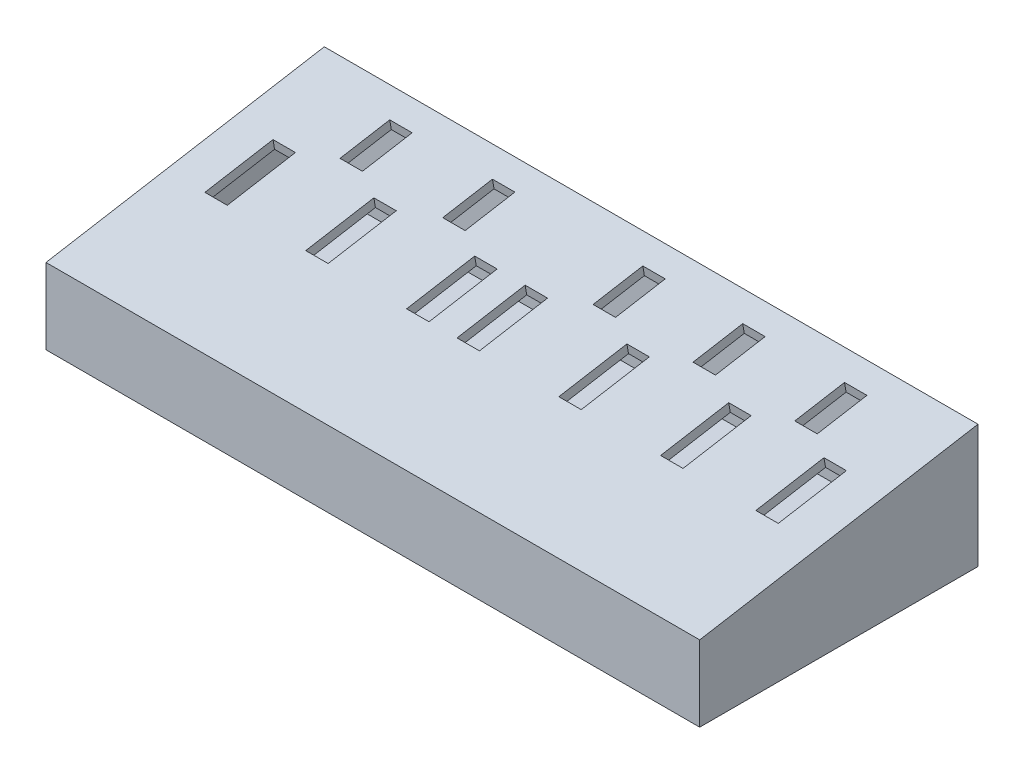
SolidWorks part; units mm, degrees
ref_plane "Alzado" through (0, 0, 0) normal (0, 0, 1) x (1, 0, 0)
ref_plane "Planta" through (0, 0, 0) normal (0, 1, 0) x (1, 0, 0)
ref_plane "Vista lateral" through (0, 0, 0) normal (1, 0, 0) x (0, 0, -1)
sketch "Croquis1" plane through (0, 0, 0) normal (0, 1, 0) x (1, 0, 0)
  line L1 (0, 0) -> (700, 0)
  line L2 (0, 0) -> (0, 298)
  line L3 (0, 298) -> (700, 298)
  line L4 (700, 0) -> (700, 298)
  dimension "D1" = 700
  dimension "D2" = 298
extrude "Saliente-Extruir1" add sketch "Croquis1" along normal blind 132
sketch "Croquis3" plane through (0, 0, 0) normal (-1, 0, 0) x (0, 0, 1)
  line L0 (0, 81) -> (-298, 132)
  line L1 (0, 132) -> (0, 0) construction
  line L2 (-298, 132) -> (0, 132)
  line L3 (-298, 132) -> (0, 132) construction
  line L4 (0, 132) -> (0, 81)
  dimension "D1" = 51
extrude "Cortar-Extruir1" cut sketch "Croquis3" against normal through all
sketch "Croquis5" plane through (0, 78.6951, 13.468) normal (0, 0.9857, 0.1687) x (1, 0, 0)
  line L0 (0, 315.9964) -> (0, 13.6638) construction
  line L1 (42, 217.6638) -> (66, 217.6638)
  line L2 (42, 217.6638) -> (42, 143.6638)
  line L3 (42, 143.6638) -> (66, 143.6638)
  line L4 (66, 217.6638) -> (66, 143.6638)
  line L5 (150, 217.6638) -> (174, 217.6638)
  line L6 (150, 217.6638) -> (150, 143.6638)
  line L7 (150, 143.6638) -> (174, 143.6638)
  line L8 (174, 217.6638) -> (174, 143.6638)
  line L9 (258, 217.6638) -> (282, 217.6638)
  line L10 (258, 217.6638) -> (258, 143.6638)
  line L11 (258, 143.6638) -> (282, 143.6638)
  line L12 (282, 217.6638) -> (282, 143.6638)
  line L13 (312, 217.6638) -> (336, 217.6638)
  line L14 (312, 217.6638) -> (312, 143.6638)
  line L15 (312, 143.6638) -> (336, 143.6638)
  line L16 (336, 217.6638) -> (336, 143.6638)
  line L17 (421, 217.6638) -> (445, 217.6638)
  line L18 (421, 217.6638) -> (421, 143.6638)
  line L19 (421, 143.6638) -> (445, 143.6638)
  line L20 (445, 217.6638) -> (445, 143.6638)
  line L21 (530, 217.6638) -> (554, 217.6638)
  line L22 (530, 217.6638) -> (530, 143.6638)
  line L23 (530, 143.6638) -> (554, 143.6638)
  line L24 (554, 217.6638) -> (554, 143.6638)
  line L25 (632, 217.6638) -> (656, 217.6638)
  line L26 (632, 217.6638) -> (632, 143.6638)
  line L27 (632, 143.6638) -> (656, 143.6638)
  line L28 (656, 217.6638) -> (656, 143.6638)
  line L29 (98, 287.6638) -> (122, 287.6638)
  line L30 (98, 287.6638) -> (98, 233.6638)
  line L31 (98, 233.6638) -> (122, 233.6638)
  line L32 (122, 287.6638) -> (122, 233.6638)
  line L33 (208, 287.6638) -> (232, 287.6638)
  line L34 (208, 287.6638) -> (208, 233.6638)
  line L35 (208, 233.6638) -> (232, 233.6638)
  line L36 (232, 287.6638) -> (232, 233.6638)
  line L37 (369, 287.6638) -> (393, 287.6638)
  line L38 (369, 287.6638) -> (369, 233.6638)
  line L39 (369, 233.6638) -> (393, 233.6638)
  line L40 (393, 287.6638) -> (393, 233.6638)
  line L41 (476, 287.6638) -> (500, 287.6638)
  line L42 (476, 287.6638) -> (476, 233.6638)
  line L43 (476, 233.6638) -> (500, 233.6638)
  line L44 (500, 287.6638) -> (500, 233.6638)
  line L45 (585, 287.6638) -> (609, 287.6638)
  line L46 (585, 287.6638) -> (585, 233.6638)
  line L47 (585, 233.6638) -> (609, 233.6638)
  line L48 (609, 287.6638) -> (609, 233.6638)
  line L49 (700, 13.6638) -> (0, 13.6638) construction
  dimension "D1" = 54
  dimension "D2" = 54
  dimension "D3" = 54
  dimension "D4" = 54
  dimension "D5" = 54
  dimension "D6" = 24
  dimension "D7" = 24
  dimension "D8" = 24
  dimension "D9" = 24
  dimension "D10" = 24
  dimension "D11" = 24
  dimension "D12" = 24
  dimension "D13" = 24
  dimension "D14" = 24
  dimension "D15" = 24
  dimension "D16" = 24
  dimension "D17" = 24
  dimension "D18" = 74
  dimension "D19" = 74
  dimension "D20" = 74
  dimension "D21" = 74
  dimension "D22" = 74
  dimension "D23" = 74
  dimension "D24" = 74
  dimension "D25" = 98
  dimension "D26" = 208
  dimension "D27" = 369
  dimension "D28" = 585
  dimension "D29" = 476
  dimension "D30" = 632
  dimension "D31" = 530
  dimension "D32" = 421
  dimension "D33" = 312
  dimension "D34" = 258
  dimension "D35" = 150
  dimension "D36" = 42
  dimension "D37" = 220
  dimension "D38" = 220
  dimension "D39" = 220
  dimension "D40" = 220
  dimension "D41" = 220
  dimension "D42" = 130
  dimension "D43" = 130
  dimension "D44" = 130
  dimension "D45" = 130
  dimension "D46" = 130
  dimension "D47" = 130
  dimension "D48" = 130
extrude "Cortar-Extruir2" cut sketch "Croquis5" against normal blind 10
shell "Vaciado2" thickness 10 removed face at (644, 99.3143, -166.2937) removed face at (597, 112.8093, -245.1472) removed face at (542, 99.3143, -166.2937) removed face at (488, 112.8093, -245.1472) removed face at (433, 99.3143, -166.2937) removed face at (381, 112.8093, -245.1472) removed face at (324, 99.3143, -166.2937) removed face at (270, 99.3143, -166.2937) removed face at (220, 112.8093, -245.1472) removed face at (54, 99.3143, -166.2937) removed face at (162, 99.3143, -166.2937) removed face at (110, 112.8093, -245.1472)
